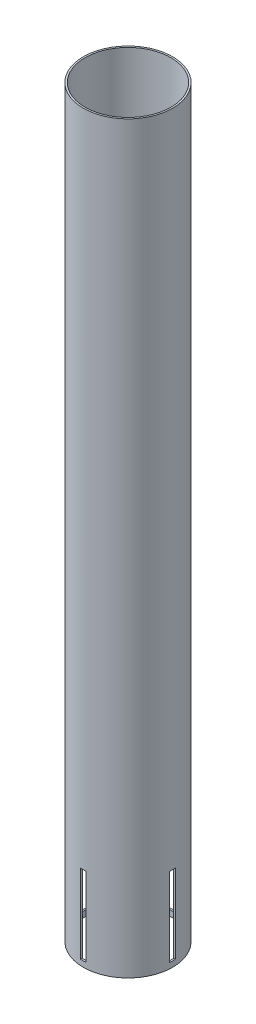
SolidWorks part; units mm, degrees
ref_plane "Front Plane" through (0, 0, 0) normal (0, 0, 1) x (1, 0, 0)
ref_plane "Top Plane" through (0, 0, 0) normal (0, 1, 0) x (1, 0, 0)
ref_plane "Right Plane" through (0, 0, 0) normal (1, 0, 0) x (0, 0, -1)
sketch "Sketch1" plane through (0, 0, 0) normal (0, 1, 0) x (1, 0, 0)
  circle A0 centre (0, 0) radius 39.6
  circle A1 centre (0, 0) radius 38.1
  dimension "D1" = 79.2
  dimension "D2" = 76.2
extrude "Boss-Extrude1" add sketch "Sketch1" along normal blind 660
sketch "Sketch2" plane through (0, 0, 0) normal (0, 0, 1) x (1, 0, 0)
  line L1 (-2.5, 5) -> (2.5, 5)
  line L2 (-2.5, 5) -> (-2.5, 75)
  line L3 (-2.5, 75) -> (2.5, 75)
  line L4 (2.5, 5) -> (2.5, 75)
  point P4 (0, 5)
  dimension "D1" = 5
  dimension "D2" = 70
  dimension "D3" = 5
extrude "Cut-Extrude1" cut sketch "Sketch2" against normal through all
pattern_circular "CirPattern1" count 4 over 360 about axis through (0, 0, 0) along (0, 1, 0) of "Cut-Extrude1"
